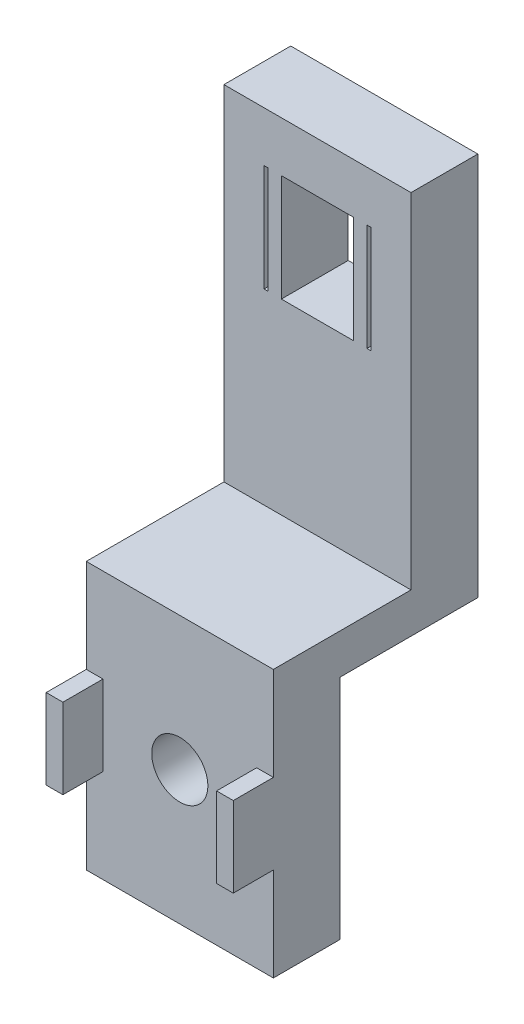
SolidWorks part; units mm, degrees
ref_plane "Front Plane" through (0, 0, 0) normal (0, 0, 1) x (1, 0, 0)
ref_plane "Top Plane" through (0, 0, 0) normal (0, 1, 0) x (1, 0, 0)
ref_plane "Right Plane" through (0, 0, 0) normal (1, 0, 0) x (0, 0, -1)
sketch "Sketch1" plane through (0, 0, 0) normal (0, 0, 1) x (1, 0, 0)
  line L0 (4.3, 42) -> (4.3, 34)
  line L1 (0, 0) -> (14, 0)
  line L2 (0, 0) -> (0, 45.75)
  line L3 (0, 45.75) -> (14, 45.75)
  line L4 (14, 0) -> (14, 45.75)
  line L9 (3, 42) -> (11, 42)
  line L10 (3, 42) -> (3, 34)
  line L11 (3, 34) -> (11, 34)
  line L12 (11, 42) -> (11, 34)
  line L13 (3.3, 42) -> (10.7, 42)
  line L14 (3.3, 42) -> (3.3, 34)
  line L15 (3.3, 34) -> (10.7, 34)
  line L16 (10.7, 42) -> (10.7, 34)
  line L17 (9.7, 42) -> (9.7, 34)
  circle A1 centre (7, 10) radius 2.1
  dimension "D7" = 4.2
  dimension "D8" = 10
  dimension "D1" = 14
  dimension "D2" = 45.75
  dimension "D3" = 8
  dimension "D4" = 8
  dimension "D5" = 42
  dimension "D6" = 3
  dimension "D10" = 7
  dimension "D12" = 0.3
  dimension "D13" = 0.3
  dimension "D14" = 1
  dimension "D15" = 1
extrude "Boss-Extrude3" add sketch "Sketch1" along normal blind 15.3 contours L1 L4 L3 L2 A1 L9 L13 L12 L11 L15 L10 | L9 L14 L11 L0 | L13 L17 L15 L16 region at (3.8, 38, 0) region at (10.2, 38, 0) region at (7, 21.4716, 0)
sketch "Sketch2" plane through (0, 0, 0) normal (-1, 0, 0) x (0, 0, 1)
  line L0 (15.3, 0) -> (15.3, 45.75) construction
  line L1 (0, 0) -> (10.3, 0)
  line L2 (0, 0) -> (0, 17)
  line L3 (0, 17) -> (10.3, 17)
  line L4 (10.3, 0) -> (10.3, 17)
  line L5 (15.3, 45.75) -> (5, 45.75)
  line L6 (15.3, 45.75) -> (15.3, 20)
  line L7 (15.3, 20) -> (5, 20)
  line L8 (5, 45.75) -> (5, 20)
  line L9 (0, 0) -> (0, 45.75) construction
  line L10 (15.3, 45.75) -> (0, 45.75) construction
  dimension "D1" = 5
  dimension "D2" = 5
  dimension "D3" = 17
  dimension "D4" = 3
  dimension "D5" = 0
extrude "Cut-Extrude1" cut sketch "Sketch2" against normal blind 21
sketch "Sketch3" plane through (0, 0, 15.3) normal (0, 0, 1) x (1, 0, 0)
  line L0 (0, 0) -> (0, 20) construction
  line L1 (0, 13) -> (1.25, 13)
  line L2 (0, 13) -> (0, 7)
  line L3 (0, 7) -> (1.25, 7)
  line L4 (1.25, 13) -> (1.25, 7)
  line L5 (14, 0) -> (14, 20) construction
  line L7 (12.75, 13) -> (12.75, 7)
  line L8 (12.75, 13) -> (14, 13)
  line L9 (14, 13) -> (14, 7)
  line L10 (12.75, 7) -> (14, 7)
  point P6 (1.25, 10)
  point P9 (14, 10)
  dimension "D1" = 6
  dimension "D2" = 0
  dimension "D3" = 1.25
  dimension "D4" = 2
  dimension "D5" = 0
extrude "Boss-Extrude4" add sketch "Sketch3" along normal blind 3
